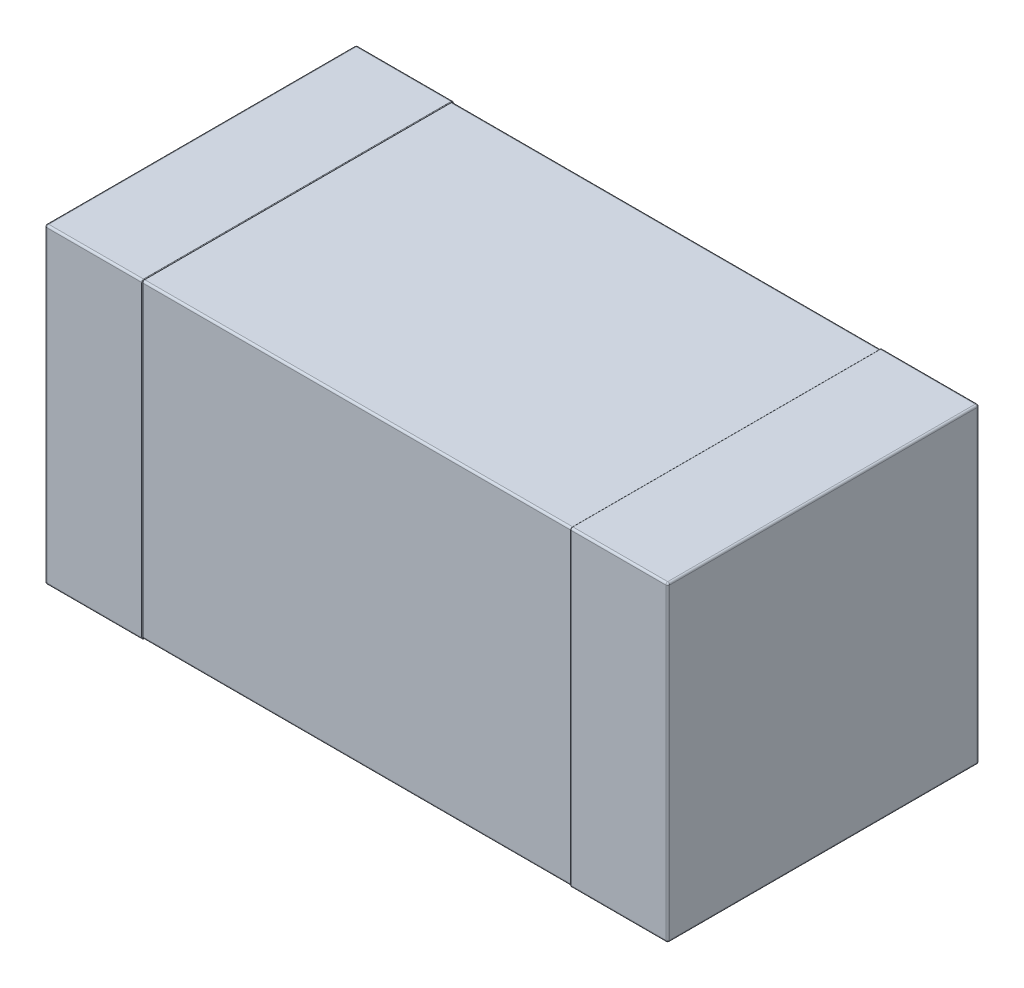
SolidWorks part; units mm, degrees
ref_plane "Top Plane" through (0, 0, 0) normal (0, 0, 1) x (1, 0, 0)
ref_plane "Front Plane" through (0, 0, 0) normal (0, 1, 0) x (1, 0, 0)
ref_plane "Side Plane" through (0, 0, 0) normal (1, 0, 0) x (0, 0, -1)
sketch "Sketch1" plane through (0, 0, 0) normal (0, 0, 1) x (1, 0, 0)
  line L1 (-1.6, 0.8) -> (1.6, 0.8)
  line L2 (-1.6, 0.8) -> (-1.6, -0.8)
  line L3 (-1.6, -0.8) -> (1.6, -0.8)
  line L4 (1.6, 0.8) -> (1.6, -0.8)
  dimension "D1" = 3.2
  dimension "D2" = 1.6
  dimension "D3" = 1.6
  dimension "D4" = 0.8
extrude "All body" add sketch "Sketch1" along normal blind 1.6
sketch "Sketch2" plane through (0, 0, 0) normal (1, 0, 0) x (0, 0, -1)
  line L14 (-0.003, 0.797) -> (-1.597, 0.797)
  line L15 (-0.003, -0.797) -> (-0.003, 0.797)
  line L16 (-1.597, -0.797) -> (-0.003, -0.797)
  line L17 (-1.597, 0.797) -> (-1.597, -0.797)
  line L18 (-0.003, 0.797) -> (-1.597, 0.797)
  line L19 (-0.003, -0.797) -> (-0.003, 0.797)
  line L20 (-1.597, -0.797) -> (-0.003, -0.797)
  line L21 (-1.597, 0.797) -> (-1.597, -0.797)
  dimension "D1" = 0.003
extrude "Cut out the body for pin" cut sketch "Sketch2" against normal blind 1.1 and the other way blind 1.1 flip side to cut
fillet "Body fillet" radius 0.01 4 edges at (0, 0.797, 0.003) (0, 0.797, 1.597) (0, -0.797, 0.003) (0, -0.797, 1.597)
fillet "Pin fillet a" radius 0.01 16 edges at (1.6, -0.8, 0.8) (1.6, 0, 1.6) (1.6, 0.8, 0.8) (1.6, 0, 0) (-1.6, 0.8, 0.8) (-1.6, 0, 1.6) (-1.6, -0.8, 0.8) (-1.6, 0, 0) (1.35, 0.8, 1.6) (1.35, -0.8, 1.6) (1.35, -0.8, 0) (1.35, 0.8, 0) (-1.35, 0.8, 0) (-1.35, -0.8, 0) (-1.35, 0.8, 1.6) (-1.35, -0.8, 1.6)
fillet "Pin fillet b" radius 0.003 16 edges at (1.1, -0.7971, 1.5971) (1.1, -0.8, 0.8) (1.1, -0.7971, 0.0029) (1.1, 0, 0) (1.1, 0.7971, 0.0029) (1.1, 0.8, 0.8) (1.1, 0.7971, 1.5971) (-1.1, -0.7971, 1.5971) (-1.1, -0.8, 0.8) (-1.1, -0.7971, 0.0029) (-1.1, 0, 0) (-1.1, 0.7971, 0.0029) (-1.1, 0.8, 0.8) (-1.1, 0.7971, 1.5971) (1.1, 0, 1.6) (-1.1, 0, 1.6)
